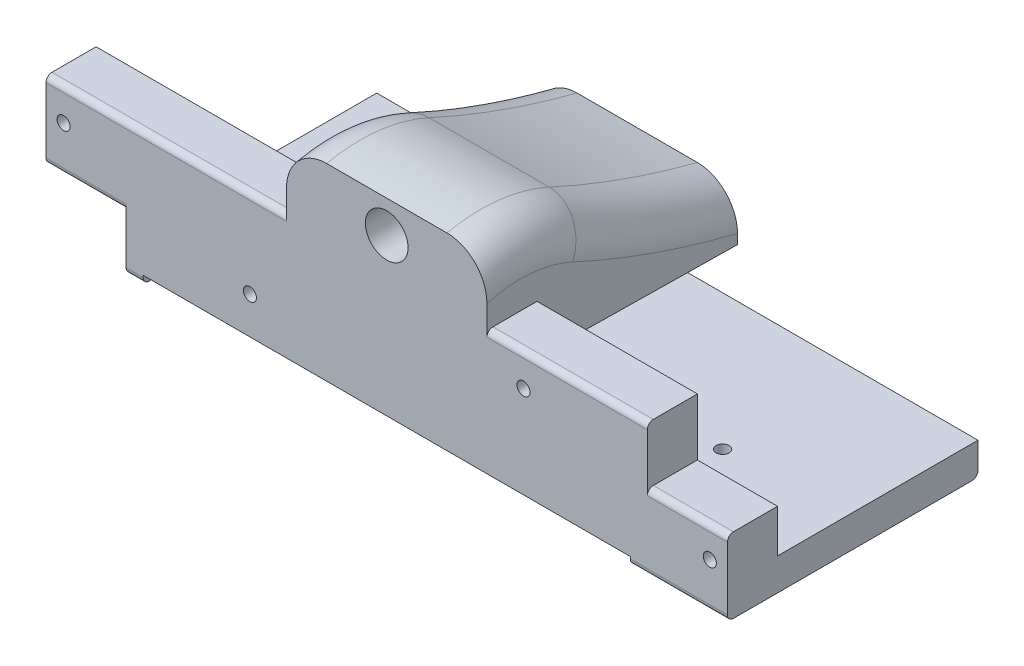
SolidWorks part; units mm, degrees
ref_plane "Front Plane" through (0, 0, 0) normal (0, 0, 1) x (1, 0, 0)
ref_plane "Top Plane" through (0, 0, 0) normal (0, 1, 0) x (1, 0, 0)
ref_plane "Right Plane" through (0, 0, 0) normal (1, 0, 0) x (0, 0, -1)
sketch "Sketch1" plane through (0, 0, 0) normal (0, 1, 0) x (1, 0, 0)
  line L1 (-43.18, -15.875) -> (43.18, -15.875)
  line L2 (-43.18, -15.875) -> (-43.18, 15.875)
  line L3 (-43.18, 15.875) -> (43.18, 15.875)
  line L4 (43.18, -15.875) -> (43.18, 15.875)
  line L5 (-43.18, -15.875) -> (43.18, 15.875) construction
  line L6 (-43.18, 15.875) -> (43.18, -15.875) construction
  point P0 (0, 0)
  dimension "D1" = 31.75
  dimension "D2" = 86.36
extrude "Boss-Extrude1" add sketch "Sketch1" along normal blind 16.764
sketch "Sketch2" plane through (-43.18, 0, 0) normal (-1, 0, 0) x (0, 0, 1)
  line L0 (-15.875, 16.764) -> (-15.875, 0) construction
  line L1 (-15.875, 10.414) -> (9.525, 10.414)
  line L2 (-15.875, 10.414) -> (-15.875, 4.064)
  line L3 (-15.875, 4.064) -> (9.525, 4.064)
  line L4 (9.525, 10.414) -> (9.525, 4.064)
  dimension "D1" = 6.35
  dimension "D2" = 25.4
  dimension "D3" = 4.064
extrude "Cut-Extrude1" cut sketch "Sketch2" against normal up to surface (86.36 mm away) up to face at (43.18, 8.382, 0)
sketch "Sketch3" plane through (-43.18, 0, 0) normal (-1, 0, 0) x (0, 0, 1)
  line L0 (9.525, 10.414) -> (-15.875, 10.414) construction
  line L1 (-15.875, 16.764) -> (9.525, 16.764)
  line L2 (-15.875, 16.764) -> (-15.875, 10.414)
  line L3 (-15.875, 10.414) -> (9.525, 10.414)
  line L4 (9.525, 16.764) -> (9.525, 10.414)
  dimension "D1" = 25.4
extrude "Cut-Extrude2" cut sketch "Sketch3" against normal blind 50.8
mirror "Mirror1" about plane through (0, 0, 0) normal (1, 0, 0) of "Cut-Extrude2"
sketch "Sketch5" plane through (0, 0, 0) normal (0, -1, 0) x (1, 0, 0)
  line L0 (-27.9908, 1.2954) -> (27.9908, 1.2954) construction
  line L1 (-43.18, 15.875) -> (43.18, 15.875) construction
  line L3 (-30.861, 15.875) -> (30.861, 15.875)
  line L4 (-30.861, 15.875) -> (-30.861, -1.2446)
  line L5 (-30.861, -1.2446) -> (30.861, -1.2446)
  line L6 (30.861, 15.875) -> (30.861, -1.2446)
  circle A0 centre (-27.9908, 1.2954) radius 0.8192
  circle A1 centre (27.9908, 1.2954) radius 0.8192
  point P0 (-27.9908, 1.2954)
  point P1 (27.9908, 1.2954)
  point P2 (0, 1.2954)
  point P12 (0, -1.2446)
  point P18 (0, -1.2446)
  line M3 (43.18, 15.875) -> (-43.18, 15.875)
  dimension "D5" = 1.6383
  dimension "D6" = 1.6383
  dimension "D1" = 2.54
  dimension "D2" = 55.9816
  dimension "D3" = 17.1196
  dimension "D4" = 61.722
extrude "Cut-Extrude3" cut sketch "Sketch5" against normal blind 1.016 contours L6 L4 L5 A0 A1 M3 | A0 | A1 region at (0, 0, 7.3393) region at (-27.9908, 0, 1.2954) region at (27.9908, 0, 1.2954)
extrude "Cut-Extrude4" cut sketch "Sketch5<3>" against normal through all contours A0 | A1 region at (-27.9908, 0, 1.2954) region at (27.9908, 0, 1.2954)
sketch "Sketch5<3>" plane through (0, 0, 0) normal (0, -1, 0) x (1, 0, 0) same geometry as "Sketch5"
sketch "Sketch6" plane through (0, 0, 15.875) normal (0, 0, 1) x (1, 0, 0)
  line L0 (-43.18, 0) -> (-30.861, 0) construction
  line L1 (-43.18, 14.5923) -> (-16.2179, 14.5923)
  line L2 (-43.18, 14.5923) -> (-43.18, 0)
  line L3 (-43.18, 0) -> (-16.2179, 0)
  line L4 (-16.2179, 14.5923) -> (-16.2179, 0)
  line L5 (-40.9448, 12.6873) -> (-17.3355, 12.6873) construction
  line L6 (-40.9448, 12.6873) -> (-40.9448, 5.715) construction
  line L7 (-40.9448, 5.715) -> (-17.3355, 5.715) construction
  line L8 (-17.3355, 12.6873) -> (-17.3355, 5.715) construction
  line L9 (-43.18, 16.764) -> (-43.18, 0) construction
  line L10 (16.2179, 14.5923) -> (43.18, 14.5923)
  line L11 (-16.2179, 14.5923) -> (-26.3779, 14.5923)
  line L12 (-16.2179, 14.5923) -> (-16.2179, 9.5123)
  line L13 (-16.2179, 9.5123) -> (-26.3779, 9.5123)
  line L14 (-26.3779, 14.5923) -> (-26.3779, 9.5123)
  line L15 (-43.18, 0) -> (-33.02, 0)
  line L16 (-43.18, 0) -> (-43.18, 6.985)
  line L17 (-43.18, 6.985) -> (-33.02, 6.985)
  line L18 (-33.02, 0) -> (-33.02, 6.985)
  line L19 (16.2179, 14.5923) -> (16.2179, 0)
  line L20 (16.2179, 0) -> (43.18, 0)
  line L21 (43.18, 14.5923) -> (43.18, 0)
  line L22 (17.3355, 12.6873) -> (40.9448, 12.6873) construction
  line L23 (17.3355, 12.6873) -> (17.3355, 5.715) construction
  line L24 (17.3355, 5.715) -> (40.9448, 5.715) construction
  line L25 (40.9448, 12.6873) -> (40.9448, 5.715) construction
  line L26 (43.18, 14.5923) -> (33.02, 14.5923)
  line L27 (43.18, 14.5923) -> (43.18, 9.5123)
  line L28 (43.18, 9.5123) -> (33.02, 9.5123)
  line L29 (33.02, 14.5923) -> (33.02, 9.5123)
  line L30 (16.2179, 0) -> (26.3779, 0)
  line L31 (16.2179, 0) -> (16.2179, 6.985)
  line L32 (16.2179, 6.985) -> (26.3779, 6.985)
  line L33 (26.3779, 0) -> (26.3779, 6.985)
  line L34 (30.861, 0) -> (43.18, 0) construction
  line L35 (43.18, 16.764) -> (43.18, 0) construction
  line L37 (33.02, 14.5923) -> (43.18, 14.5923)
  line L38 (33.02, 14.5923) -> (33.02, 16.764)
  line L39 (33.02, 16.764) -> (43.18, 16.764)
  line L40 (43.18, 14.5923) -> (43.18, 16.764)
  circle A0 centre (-40.9448, 12.6873) radius 0.8255
  circle A1 centre (-17.3355, 12.6873) radius 0.8255
  circle A2 centre (-17.3355, 5.715) radius 0.8255
  circle A3 centre (-40.9448, 5.715) radius 0.8255
  circle A4 centre (17.3355, 12.6873) radius 0.8255
  circle A5 centre (40.9448, 12.6873) radius 0.8255
  circle A6 centre (40.9448, 5.715) radius 0.8255
  circle A7 centre (17.3355, 5.715) radius 0.8255
  line M11 (43.18, 0) -> (43.18, 16.764)
  line M12 (43.18, 16.764) -> (-43.18, 16.764)
  line M14 (-43.18, 0) -> (-30.861, 0)
  dimension "D7" = 1.651
  dimension "D8" = 1.651
  dimension "D9" = 1.651
  dimension "D10" = 1.651
  dimension "D21" = 1.651
  dimension "D22" = 1.651
  dimension "D23" = 1.651
  dimension "D24" = 1.651
  dimension "D1" = 26.9621
  dimension "D2" = 14.5923
  dimension "D3" = 1.1176
  dimension "D4" = 2.2352
  dimension "D5" = 1.905
  dimension "D6" = 5.715
  dimension "D11" = 10.16
  dimension "D12" = 5.08
  dimension "D13" = 10.16
  dimension "D14" = 6.985
  dimension "D15" = 26.9621
  dimension "D16" = 14.5923
  dimension "D17" = 1.1176
  dimension "D18" = 2.2352
  dimension "D19" = 1.905
  dimension "D20" = 5.715
  dimension "D25" = 10.16
  dimension "D26" = 5.08
  dimension "D27" = 10.16
  dimension "D28" = 6.985
extrude "Cut-Extrude8" cut sketch "Sketch6" against normal up to surface (31.75 mm away) contours A5 | L10 L29 L28 L21 A5 | A4 | A6 | L18 L17 L2 A3 M14 | A3 | A2 | A0 | L38 L10 M11 M12 region at (-38.0115, 3.4234, 15.875) region at (38.1, 15.6782, 15.875) region at (37.9769, 12.0248, 15.875) region at (-40.9448, 12.6873, 15.875) region at (-17.3355, 5.715, 15.875) region at (-40.9448, 5.715, 15.875) region at (17.3355, 12.6873, 15.875) region at (40.9448, 12.6873, 15.875) region at (40.9448, 5.715, 15.875) up to face at (0, 2.032, -15.875)
sketch "Sketch7" plane through (0, 0, 9.525) normal (0, 0, -1) x (-1, 0, 0)
  line L0 (-33.02, 16.764) -> (43.18, 16.764) construction
  line L1 (-12.7, 9.144) -> (12.7, 9.144)
  line L2 (-12.7, 9.144) -> (-12.7, 16.764)
  line L3 (-12.7, 16.764) -> (12.7, 16.764)
  line L4 (12.7, 9.144) -> (12.7, 16.764)
  line L5 (-12.7, 9.144) -> (12.7, 16.764) construction
  line L6 (-12.7, 16.764) -> (12.7, 9.144) construction
  line L7 (-43.18, 4.064) -> (33.02, 4.064) construction
  point P0 (0, 12.954)
  dimension "D1" = 5.08
  dimension "D2" = 25.4
extrude "Boss-Extrude2" add sketch "Sketch7" along normal blind 25.4
sketch "Sketch8" plane through (-12.7, 0, 0) normal (-1, 0, 0) x (0, 0, 1)
  line L0 (-15.875, 10.287) -> (9.525, 10.668)
  line L1 (-15.875, 9.144) -> (-15.875, 16.764) construction
  line L3 (-15.875, 9.144) -> (9.525, 9.144) construction
  line L5 (9.525, 9.144) -> (9.525, 16.764) construction
  line L6 (-15.875, 10.287) -> (-15.875, 9.144)
  line L7 (-15.875, 9.144) -> (9.525, 9.144)
  line L8 (9.525, 9.144) -> (9.525, 10.668)
  dimension "D1" = 1.143
  dimension "D2" = 1.524
extrude "Cut-Extrude9" cut sketch "Sketch8" against normal blind 25.4
fillet "Fillet1" radius 0.381 1 edges at (0, 10.668, 9.525)
sketch "Sketch11" plane through (0, 0, 15.875) normal (0, 0, 1) x (1, 0, 0)
  line L1 (-43.18, 16.764) -> (33.02, 16.764) construction
  line L2 (-12.7, 16.764) -> (12.7, 16.764)
  line L3 (-12.7, 16.764) -> (-12.7, 25.654)
  line L4 (-12.7, 25.654) -> (12.7, 25.654)
  line L5 (12.7, 16.764) -> (12.7, 25.654)
  line L6 (-12.7, 16.764) -> (12.7, 25.654) construction
  line L7 (-12.7, 25.654) -> (12.7, 16.764) construction
  point P0 (0, 21.209)
  dimension "D1" = 8.89
  dimension "D2" = 25.4
extrude "Boss-Extrude5" add sketch "Sketch11" against normal up to surface (31.75 mm away) up to face at (0, 13.5255, -15.875)
fillet "Fillet2" radius 0.762 7 edges at (-31.9405, 0, 15.875) (37.0205, 0, 15.875) (5.08, 0, -15.875) (38.1, 9.5123, 15.875) (-38.1, 6.985, 15.875) (22.86, 16.764, 15.875) (-27.94, 16.764, 15.875)
sketch "Sketch10" plane through (0, 0, 15.875) normal (0, 0, 1) x (1, 0, 0)
  line L0 (-12.7, 25.654) -> (12.7, 16.002) construction
  line L1 (12.7, 25.654) -> (-12.7, 16.002) construction
  circle A0 centre (0, 20.828) radius 2.7051
  point P10 (0, 20.828)
  dimension "D1" = 5.4102
sketch "Sketch12" plane through (-12.7, 0, 0) normal (-1, 0, 0) x (0, 0, 1)
  line L0 (-989.8058, 16.764) -> (49010.1942, 16.764) construction
  line L2 (-15.875, 10.287) -> (-15.875, 25.654) construction
  line L3 (9.525, 16.764) -> (15.113, 16.764) construction
  line L4 (-15.875, 25.654) -> (15.875, 25.654) construction
  line L5 (15.875, 18.1229) -> (15.875, 23.5331) construction
  line L6 (15.875, 25.654) -> (15.875, 16.002) construction
  line L7 (-15.875, 16.764) -> (-15.875, 25.654)
  line L8 (-15.875, 25.654) -> (15.875, 25.654)
  line L9 (15.875, 25.654) -> (15.875, 16.002) construction
  line L10 (15.875, 25.654) -> (15.875, 24.9119)
  arc A0 (2.9008, 23.4479) -> (15.875, 24.9119) centre (11.6067, 4.5168) cw
  arc A1 (2.9008, 23.4479) -> (-15.875, 16.764) centre (-43.9222, 125.2654) cw
  point P1 (-15.875, 16.764)
  dimension "D1" = 112.0679
  dimension "D2" = 20.837
  dimension "D3" = 12.9742
  dimension "D4" = 2.2061
extrude "Cut-Extrude10" cut sketch "Sketch12" against normal up to surface (25.4 mm away) up to face at (12.7, 16.5384, 5.4424)
fillet "Fillet4" radius 5.08 4 edges at (12.7, 19.6877, -6.3382) (-12.7, 19.6877, -6.3382) (12.7, 25.2224, 9.2703) (-12.7, 25.2224, 9.2703)
extrude "Cut-Extrude11" cut sketch "Sketch10" against normal blind 8.001
